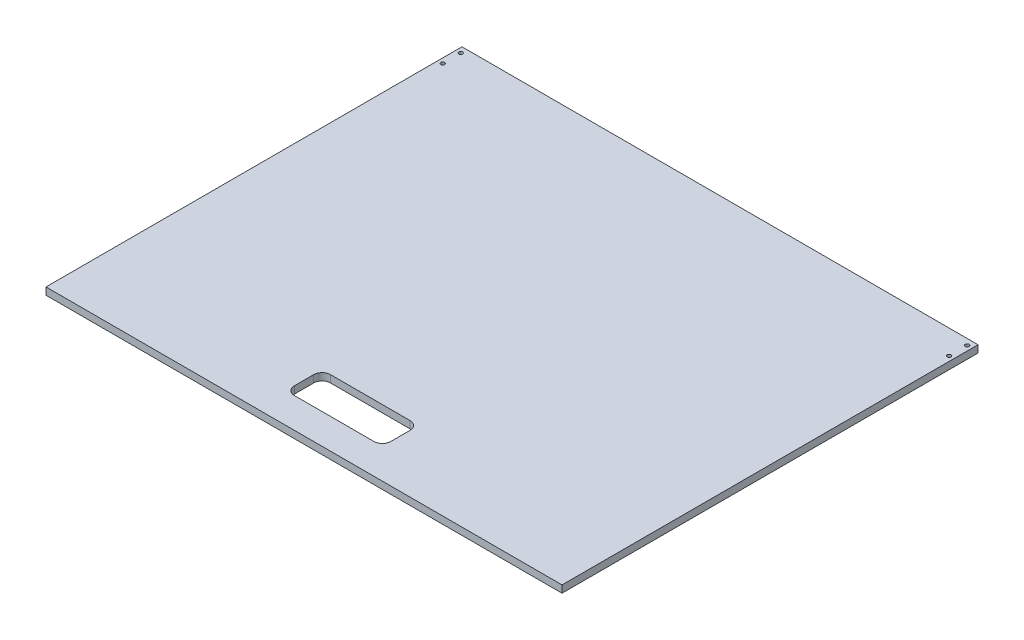
SolidWorks part; units mm, degrees
ref_plane "Front Plane" through (0, 0, 0) normal (0, 0, 1) x (1, 0, 0)
ref_plane "Top Plane" through (0, 0, 0) normal (0, 1, 0) x (1, 0, 0)
ref_plane "Right Plane" through (0, 0, 0) normal (1, 0, 0) x (0, 0, -1)
sketch "Sketch1" plane through (0, 0, 0) normal (0, 1, 0) x (1, 0, 0)
  line L1 (-214, -172.5) -> (214, -172.5)
  line L2 (-214, -172.5) -> (-214, 172.5)
  line L3 (-214, 172.5) -> (214, 172.5)
  line L4 (214, -172.5) -> (214, 172.5)
  line L5 (-214, -172.5) -> (214, 172.5) construction
  line L6 (-214, 172.5) -> (214, -172.5) construction
  point P0 (0, 0)
  dimension "D1" = 428
  dimension "D2" = 345
extrude "Boss-Extrude1" add sketch "Sketch1" along normal blind 6
sketch "Sketch2" plane through (0, 0, 0) normal (0, -1, 0) x (1, 0, 0)
  line L0 (214, -172.5) -> (-214, -172.5) construction
  line L1 (214, 172.5) -> (214, -172.5) construction
  circle A0 centre (210, -152.5) radius 1.6
  circle A1 centre (210, -167.5) radius 1.6
  dimension "D1" = 5
  dimension "D3" = 3.2
  dimension "D2" = 15
  dimension "D4" = 4
extrude "Cut-Extrude1" cut sketch "Sketch2" against normal through all
mirror "Mirror1" about plane through (0, 0, 0) normal (1, 0, 0) of "Cut-Extrude1"
sketch "Sketch3" plane through (0, 6, 0) normal (0, 1, 0) x (1, 0, 0)
  line L0 (-214, -172.5) -> (214, -172.5) construction
  line L1 (-33, -147.5) -> (33, -147.5)
  line L2 (-40, -140.5) -> (-40, -124.5)
  line L3 (-33, -117.5) -> (33, -117.5)
  line L4 (40, -140.5) -> (40, -124.5)
  line L5 (-40, -147.5) -> (40, -117.5) construction
  line L6 (-40, -117.5) -> (40, -147.5) construction
  arc A0 (-40, -124.5) -> (-33, -117.5) centre (-33, -124.5) cw
  arc A1 (-33, -147.5) -> (-40, -140.5) centre (-33, -140.5) cw
  arc A2 (33, -147.5) -> (40, -140.5) centre (33, -140.5) ccw
  arc A3 (33, -117.5) -> (40, -124.5) centre (33, -124.5) cw
  point P0 (0, -132.5)
  dimension "D4" = 7
  dimension "D1" = 25
  dimension "D2" = 80
  dimension "D3" = 30
extrude "Cut-Extrude2" cut sketch "Sketch3" against normal through all
